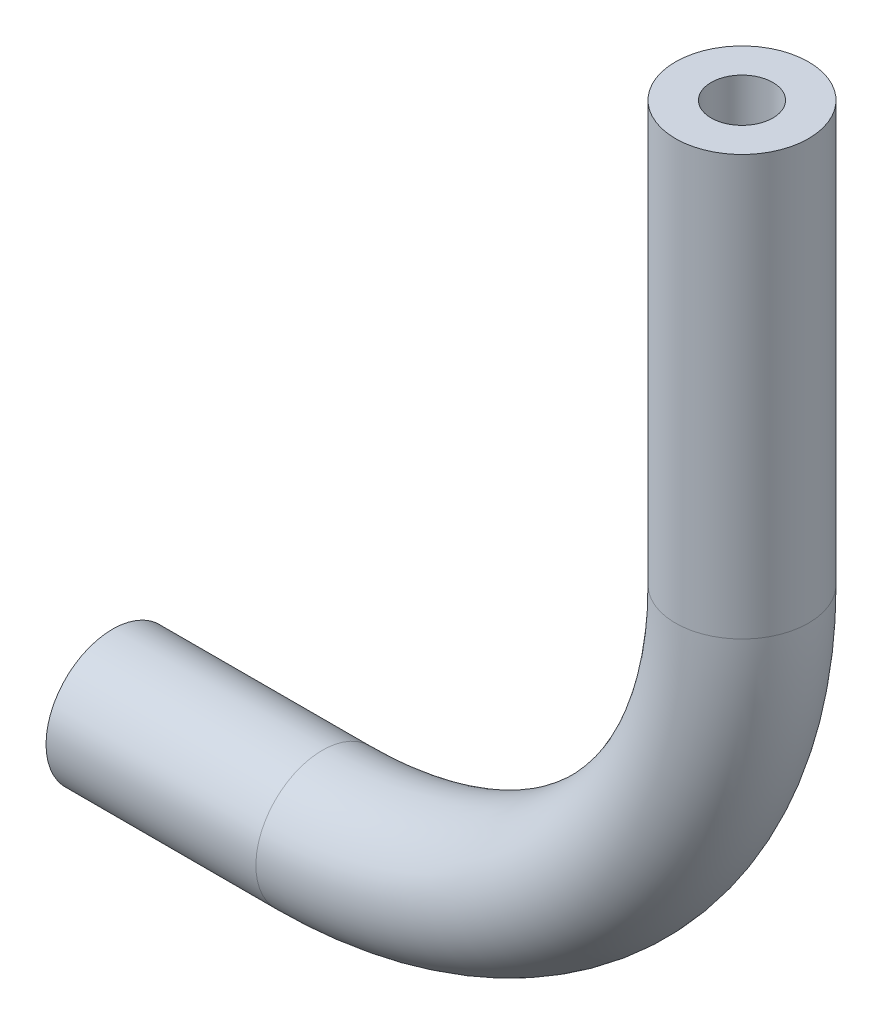
SolidWorks part; units mm, degrees
material "Plain Carbon Steel"
ref_plane "Piano frontale" through (0, 0, 0) normal (0, 0, 1) x (1, 0, 0)
ref_plane "Piano superiore" through (0, 0, 0) normal (0, 1, 0) x (1, 0, 0)
ref_plane "Piano destro" through (0, 0, 0) normal (1, 0, 0) x (0, 0, -1)
sketch3d "Schizzo3D1"
  line L0 (0, 20, 0) -> (0, 10, 0)
  line L2 (-10, 0, 0) -> (-15, 0, 0)
  line L4 (-25, 0, 0) -> (-25, 17.7988, 0) construction
  arc A0 (0, 10, 0) -> (-10, 0, 0) centre (-10, 10, 0) ccw
  point P8 (0, 0, 0)
  point P9 (-10, 10, -10)
  point P12 (-25, 0, 0)
  dimension "D4" = 10
  dimension "D1" = 20
  dimension "D5" = 25
sweep "Sweep-Sottile1" add path "Schizzo3D1" circular profile diameter 3.17 parameters "D1"=0.85, "D3"=3.17
